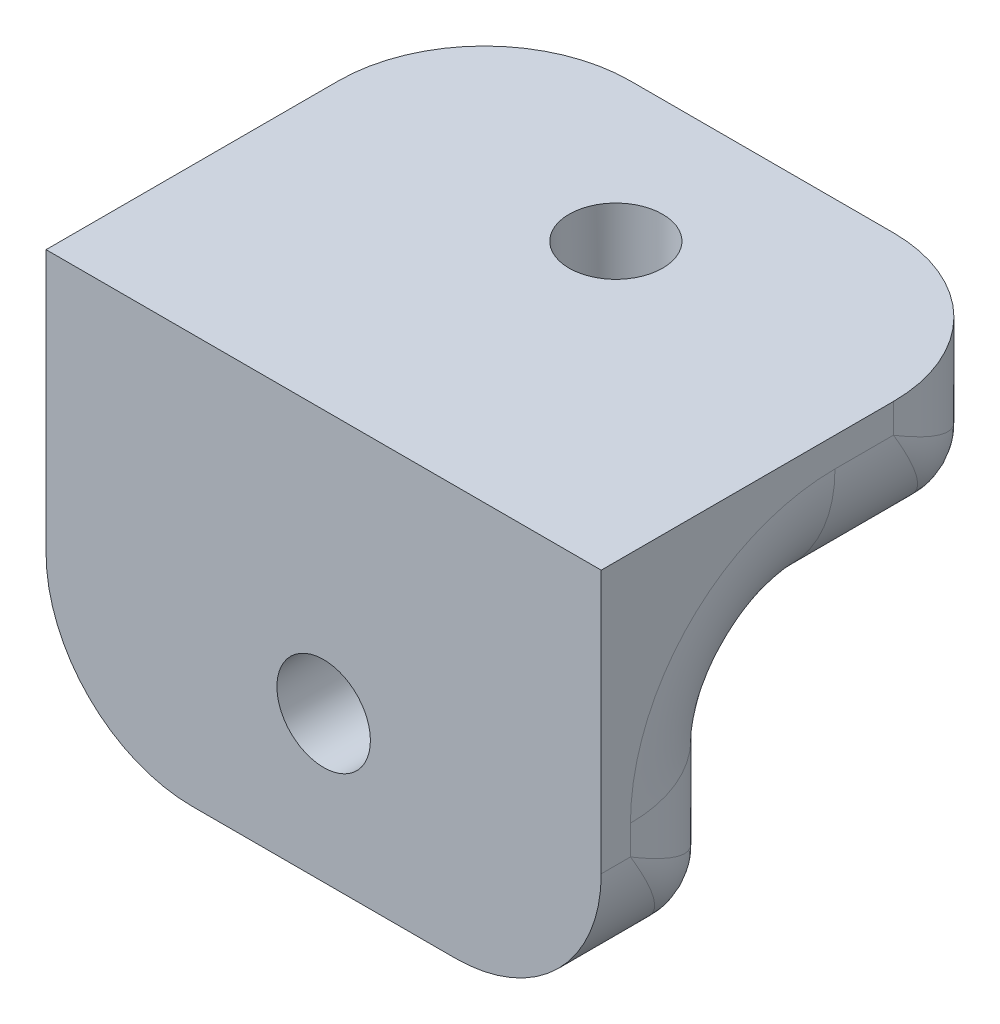
SolidWorks part; units mm, degrees
material "ABS"
ref_plane "Front" through (0, 0, 0) normal (0, 0, 1) x (1, 0, 0)
ref_plane "Top" through (0, 0, 0) normal (0, 1, 0) x (1, 0, 0)
ref_plane "Right" through (0, 0, 0) normal (1, 0, 0) x (0, 0, -1)
sketch "Esquisse1" plane through (0, 0, 0) normal (1, 0, 0) x (0, 0, -1)
  line L0 (15, 0) -> (0, 0)
  line L1 (0, 0) -> (0, -14)
  dimension "D1" = 90
  dimension "D2" = 15
  dimension "D3" = 14
extrude "Extru.-Mince1" add sketch "Esquisse1" along normal mid plane 19 thin thin type one direction reverse wall 6
fillet "Congé2" radius 2 3 edges at (0, -14, -6) (0, -6, -15) (0, -6, -6)
sketch "Esquisse2" plane through (0, 0, 0) normal (0, 1, 0) x (1, 0, 0)
  line L3 (9.5, 0) -> (-9.5, 0) construction
  line L4 (9.5, 15) -> (-9.5, 15) construction
  circle A1 centre (0, 10) radius 1.6
  dimension "D1" = 10
  dimension "D2" = 5
  dimension "D3" = 3.2
extrude "Enlèv. mat.-Extru.1" cut sketch "Esquisse2" against normal through all
sketch "Esquisse3" plane through (0, 0, 0) normal (0, 0, 1) x (1, 0, 0)
  line L0 (9.5, -14) -> (-9.5, -14) construction
  line L2 (9.5, 0) -> (-9.5, 0) construction
  circle A0 centre (0, -9) radius 1.6
  dimension "D1" = 5
  dimension "D2" = 3.2
  dimension "D3" = 9
extrude "Enlèv. mat.-Extru.2" cut sketch "Esquisse3" against normal through all
sketch "Esquisse4" plane through (0, 0, 0) normal (0, 1, 0) x (1, 0, 0)
  line L1 (-3.1754, 10) -> (-1.5877, 7.25)
  line L2 (-1.5877, 7.25) -> (1.5877, 7.25)
  line L3 (1.5877, 7.25) -> (3.1754, 10)
  line L4 (3.1754, 10) -> (1.5877, 12.75)
  line L5 (1.5877, 12.75) -> (-1.5877, 12.75)
  line L6 (-1.5877, 12.75) -> (-3.1754, 10)
  circle A2 centre (0, 10) radius 2.75 construction
  dimension "D1" = 5.5
extrude "Enlèv. mat.-Extru.3" cut sketch "Esquisse4" against normal through all from offset 2.5 offset against normal yes
sketch "Esquisse5" plane through (0, 0, 0) normal (0, 0, 1) x (1, 0, 0)
  line L13 (-1.5877, -6.25) -> (-3.1754, -9)
  line L14 (-3.1754, -9) -> (-1.5877, -11.75)
  line L15 (-1.5877, -11.75) -> (1.5877, -11.75)
  line L16 (1.5877, -11.75) -> (3.1754, -9)
  line L17 (3.1754, -9) -> (1.5877, -6.25)
  line L18 (1.5877, -6.25) -> (-1.5877, -6.25)
  circle A3 centre (0, -9) radius 2.75 construction
  dimension "D1" = 5.5
extrude "Enlèv. mat.-Extru.4" cut sketch "Esquisse5" against normal blind 8 from offset 3 offset against normal yes
fillet "Congé1" radius 5 14 edges at (9.5, -2, -15) (-9.5, -2, -15) (9.5, -14, -2) (9.5, -13.4142, -5.4142) (9.5, -10, -6) (9.5, -6.5858, -6.5858) (9.5, -6, -10.5) (9.5, -5.4142, -14.4142) (-9.5, -14, -2) (-9.5, -13.4142, -5.4142) (-9.5, -10, -6) (-9.5, -6.5858, -6.5858) (-9.5, -6, -10.5) (-9.5, -5.4142, -14.4142)
sketch "Esquisse6" plane through (0, 0, 0) normal (0, 1, 0) x (1, 0, 0)
  line L0 (4.5, 15) -> (-4.5, 15) construction
  line L1 (-2.35, 15) -> (2.35, 15)
  line L2 (-2.35, 15) -> (-2.35, 0)
  line L3 (-2.35, 0) -> (2.35, 0)
  line L4 (2.35, 15) -> (2.35, 0)
  circle A0 centre (0, 10) radius 1.6 construction
  circle A1 centre (0, 10) radius 1.6
  dimension "D1" = 4.7
extrude "Boss.-Extru.1" [suppressed] add sketch "Esquisse6" along normal blind 1.5
fillet "Congé3" [suppressed] radius 0.5
sketch "Esquisse7" plane through (0, 0, 0) normal (0, 0, 1) x (1, 0, 0)
  circle A1 centre (0, -9) radius 1.6 construction
  circle A2 centre (0, -9) radius 1.6
extrude "Boss.-Extru.2" [suppressed] add sketch "Esquisse7" against normal blind 0.2
sketch "Sketch1" [suppressed] plane through (0, 0, -15) normal (0, 0, -1) x (-1, 0, 0)
  line L1 (-2.35, 0) -> (3.0183, 0)
  line L2 (-2.35, 0) -> (-2.35, 3.1233)
  line L3 (-2.35, 3.1233) -> (3.0183, 3.1233)
  line L4 (3.0183, 0) -> (3.0183, 3.1233)
extrude "Cut-Extrude1" [suppressed] cut sketch "Sketch1" against normal through all
